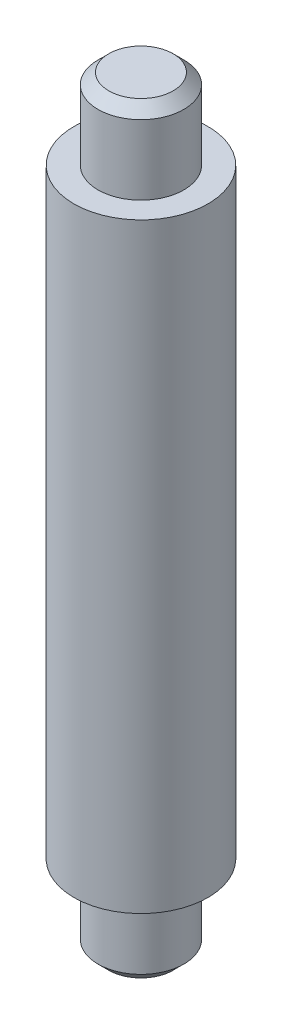
SolidWorks part; units mm, degrees
ref_plane "Front Plane" through (0, 0, 0) normal (0, 0, 1) x (1, 0, 0)
ref_plane "Top Plane" through (0, 0, 0) normal (0, 1, 0) x (1, 0, 0)
ref_plane "Right Plane" through (0, 0, 0) normal (1, 0, 0) x (0, 0, -1)
sketch "Sketch1" plane through (0, 0, 0) normal (0, 1, 0) x (1, 0, 0)
  circle A0 centre (0, 0) radius 1.25
  dimension "D1" = 2.5
extrude "Boss-Extrude1" add sketch "Sketch1" along normal blind 11.2 contours A0
sketch "Sketch2" plane through (0, 11.2, 0) normal (0, 1, 0) x (1, 0, 0)
  circle A0 centre (0, 0) radius 0.8
  dimension "D1" = 1.6
extrude "Boss-Extrude2" add sketch "Sketch2" along normal blind 1.5
extrude "Boss-Extrude3" add sketch "Sketch2<2>" against normal blind 1.5 from surface starting at face at (0, 0, 1.25)
sketch "Sketch2<2>" plane through (0, 11.2, 0) normal (0, 1, 0) x (1, 0, 0) same geometry as "Sketch2"
chamfer "Chamfer1" distance 0.2 angle 45 2 edges at (0, -1.5, 0.8) (0, 12.7, 0.8)
